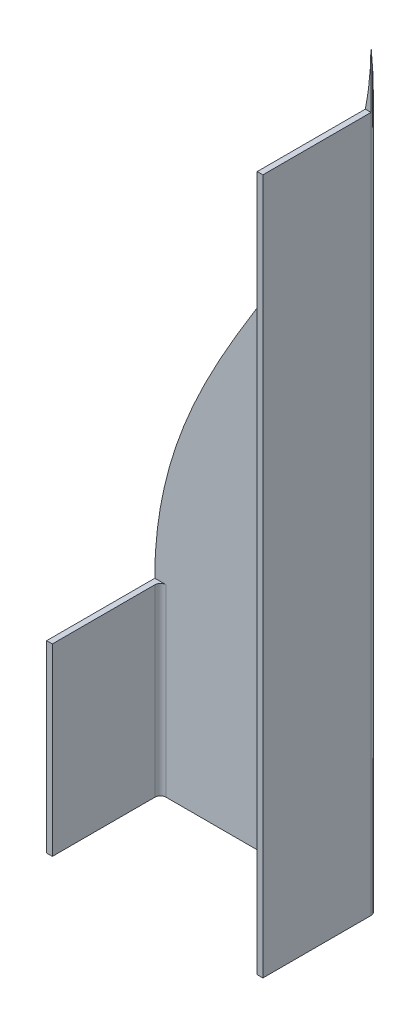
SolidWorks part; units mm, degrees
ref_plane "Front Plane" through (0, 0, 0) normal (0, 0, 1) x (1, 0, 0)
ref_plane "Top Plane" through (0, 0, 0) normal (0, 1, 0) x (1, 0, 0)
ref_plane "Right Plane" through (0, 0, 0) normal (1, 0, 0) x (0, 0, -1)
sketch "Sketch2" plane through (0, 0, 0) normal (0, 0, 1) x (1, 0, 0)
  line L0 (0, 0) -> (0, 132.34)
  line L1 (0, 0) -> (-38, 0)
  line L2 (-38, 0) -> (-38, 32.34)
  spline S0 degree 3 poles (-38, 32.34) (-38, 73.0986) (0, 96.4228) (0, 132.34) knots 0 0 0 0 1 1 1 1
  dimension "D1" = 100
  dimension "D2" = 32.34
  dimension "D3" = 38
extrude "Boss-Extrude1" add sketch "Sketch2" against normal blind 1
sketch "Sketch3" plane through (0, 0, -1) normal (0, 0, -1) x (-1, 0, 0)
  line L1 (0, 0) -> (1, 0)
  line L2 (0, 0) -> (0, 122.2327)
  line L3 (0, 122.2327) -> (1, 122.2327)
  line L4 (1, 0) -> (1, 122.2327)
  line L5 (38, 0) -> (37, 0)
  line L6 (38, 0) -> (38, 32.34)
  line L7 (38, 32.34) -> (37, 32.34)
  line L8 (37, 0) -> (37, 32.34)
  spline S0 degree 3 poles (0, 132.34) (0, 96.4228) (38, 73.0986) (38, 32.34) knots 0 0 0 0 1 1 1 1 construction
  dimension "D1" = 1
  dimension "D2" = 1
extrude "Boss-Extrude2" add sketch "Sketch3" against normal blind 20
fillet "Fillet1" radius 1 2 edges at (-37, 16.17, 0) (-1, 61.1164, 0)
fillet "Fillet2" radius 1 3 edges at (0, 66.17, -1) (-38, 16.17, -1)
